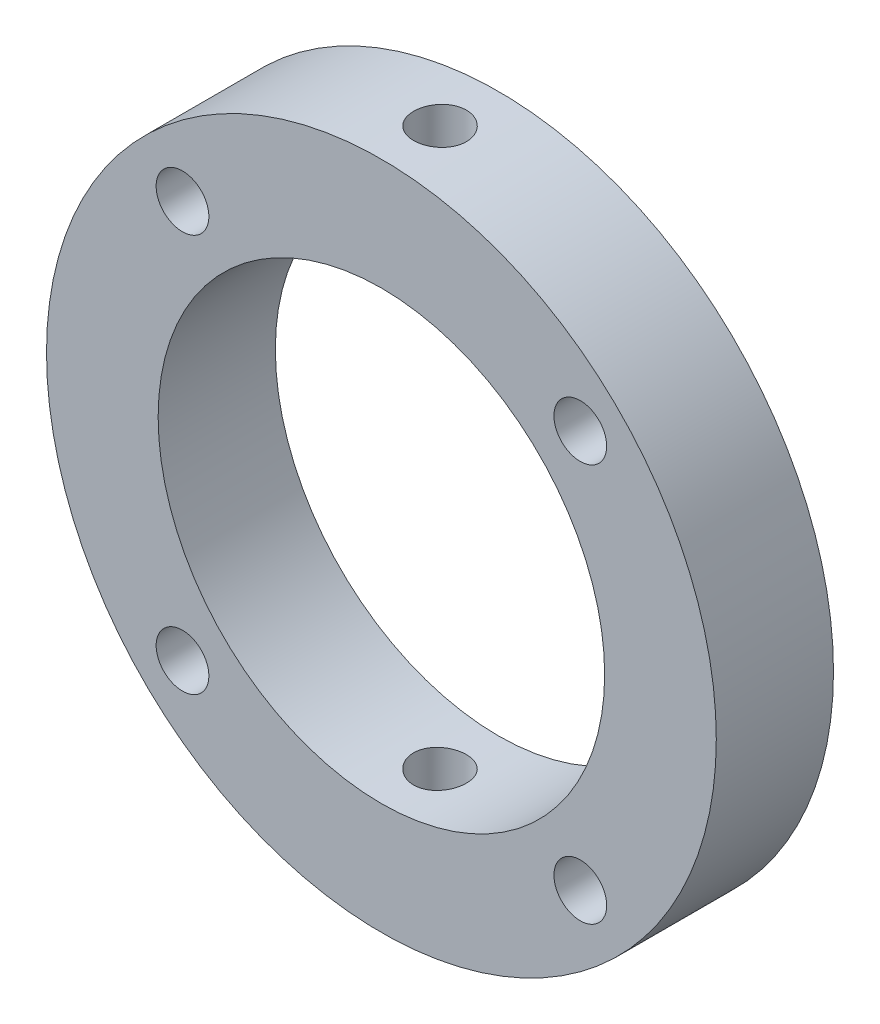
SolidWorks part; units mm, degrees
ref_plane "Front Plane" through (0, 0, 0) normal (0, 0, 1) x (1, 0, 0)
ref_plane "Top Plane" through (0, 0, 0) normal (0, 1, 0) x (1, 0, 0)
ref_plane "Right Plane" through (0, 0, 0) normal (1, 0, 0) x (0, 0, -1)
sketch "Sketch1" plane through (0, 0, 0) normal (0, 0, 1) x (1, 0, 0)
  circle A0 centre (0, 0) radius 28.575
  dimension "D1" = 57.15
extrude "Boss-Extrude1" add sketch "Sketch1" along normal blind 10
sketch "Sketch2" plane through (0, 0, 10) normal (0, 0, 1) x (1, 0, 0)
  circle A0 centre (0, 0) radius 19.05
  dimension "D1" = 38.1
extrude "Cut-Extrude1" cut sketch "Sketch2" against normal through all
ref_plane "Plane1" through (0, 28.575, 0) normal (0, 1, 0) x (1, 0, 0)
sketch "Sketch5" plane through (0, 28.575, 0) normal (0, 1, 0) x (1, 0, 0)
  circle A0 centre (0, -5) radius 2.25
  dimension "D2" = 4.5
  dimension "D1" = 5
extrude "Cut-Extrude2" cut sketch "Sketch5" against normal through all
sketch "Sketch6" plane through (0, 0, 10) normal (0, 0, 1) x (1, 0, 0)
  line L0 (0, 28.575) -> (0, -28.575) construction
  line L1 (5.5, 28.575) -> (-5.5, 28.575) construction
  line L2 (0, 0) -> (-16.9706, 16.9706) construction
  circle A1 centre (0, 0) radius 28.575 construction
  circle A3 centre (0, 0) radius 24 construction
  circle A4 centre (-16.9706, 16.9706) radius 2.25
  circle A5 centre (16.9706, 16.9706) radius 2.25
  circle A6 centre (16.9706, -16.9706) radius 2.25
  circle A7 centre (-16.9706, -16.9706) radius 2.25
  point P11 (0, 0)
  point P12 (0, 0)
  point P13 (0, 0)
  point P14 (0, 0)
  point P21 (0, 0)
  point P22 (0, 0)
  dimension "D2" = 45
  dimension "D1" = 48
  dimension "D3" = 4.5
  dimension "D4" = 4
extrude "Cut-Extrude3" cut sketch "Sketch6" against normal through all
